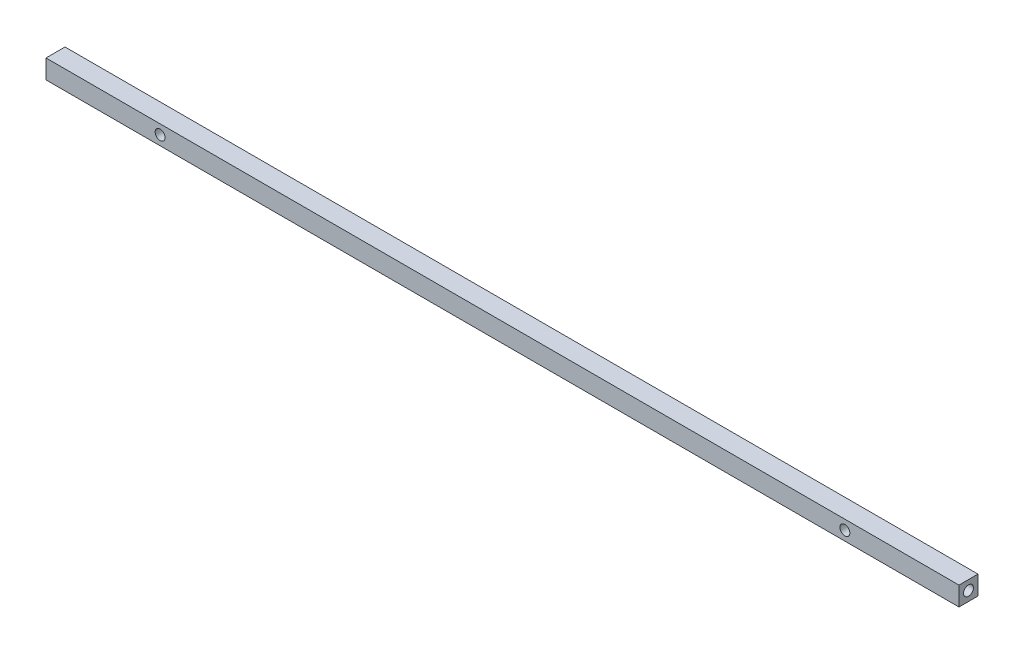
SolidWorks part; units mm, degrees
ref_plane "Front Plane" through (0, 0, 0) normal (0, 0, 1) x (1, 0, 0)
ref_plane "Top Plane" through (0, 0, 0) normal (0, 1, 0) x (1, 0, 0)
ref_plane "Right Plane" through (0, 0, 0) normal (1, 0, 0) x (0, 0, -1)
sketch "Sketch1" plane through (0, 0, 0) normal (1, 0, 0) x (0, 0, -1)
  line L5 (-3.175, -3.175) -> (3.175, -3.175)
  line L6 (-3.175, -3.175) -> (-3.175, 3.175)
  line L7 (-3.175, 3.175) -> (3.175, 3.175)
  line L8 (3.175, -3.175) -> (3.175, 3.175)
  line L9 (-3.175, -3.175) -> (3.175, 3.175) construction
  line L10 (-3.175, 3.175) -> (3.175, -3.175) construction
  point P0 (0, 0)
  dimension "D1" = 6.35
extrude "Boss-Extrude1" add sketch "Sketch1" along normal mid plane 304.8
sketch "Sketch4" plane through (152.4, 0, 0) normal (1, 0, 0) x (0, 0, -1)
  circle A0 centre (0, 0) radius 1.651
  dimension "D1" = 3.302
extrude "Cut-Extrude1" cut sketch "Sketch4" against normal blind 12.7
sketch "Sketch5" plane through (0, 0, 3.175) normal (0, 0, 1) x (1, 0, 0)
  circle A0 centre (114.3, 0) radius 1.651
  circle A1 centre (114.3, 0) radius 1.651 construction
  dimension "D1" = 3.302
extrude "Cut-Extrude2" cut sketch "Sketch5" against normal through all
mirror "Mirror1" about plane through (0, 0, 0) normal (1, 0, 0) of "Cut-Extrude1", "Cut-Extrude2"
